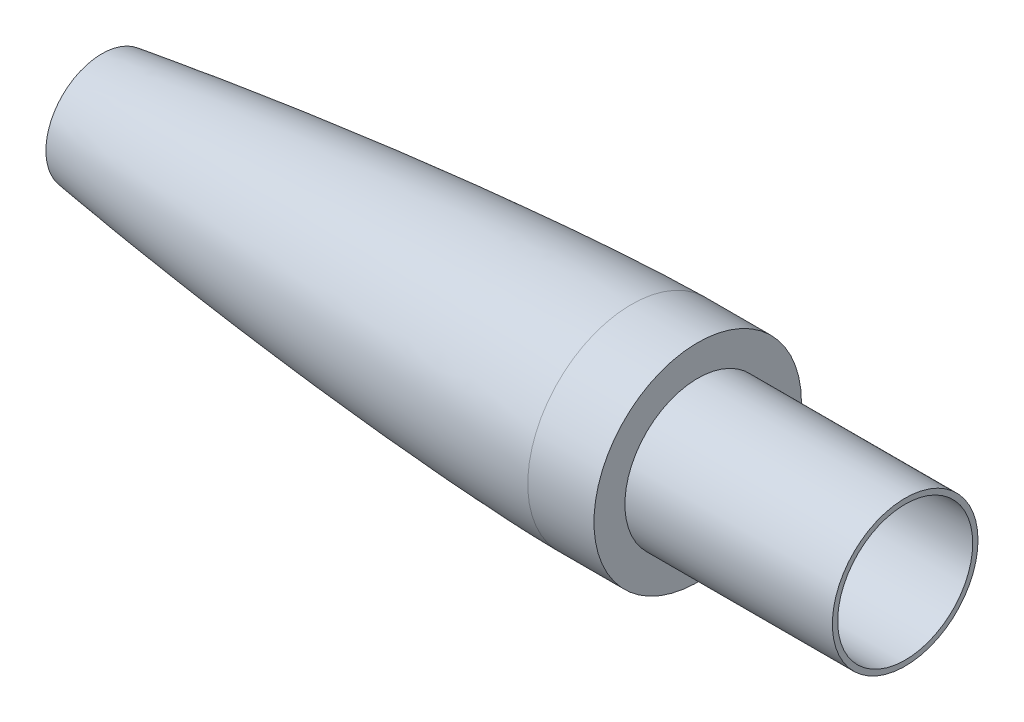
SolidWorks part; units mm, degrees
ref_plane "Front Plane" through (0, 0, 0) normal (0, 0, 1) x (1, 0, 0)
ref_plane "Top Plane" through (0, 0, 0) normal (0, 1, 0) x (1, 0, 0)
ref_plane "Right Plane" through (0, 0, 0) normal (1, 0, 0) x (0, 0, -1)
sketch "Sketch1" plane through (0, 0, 0) normal (0, 0, 1) x (1, 0, 0)
  line L0 (0, 0) -> (600, 0) construction
  line L1 (600, 0) -> (600, 78.36) construction
  line L2 (600, 78.36) -> (650, 78.36)
  line L3 (650, 78.36) -> (650, 55)
  line L4 (650, 55) -> (806.72, 55)
  line L5 (806.72, 55) -> (806.72, 0)
  line L6 (806.72, 0) -> (0, 0)
  line L7 (200, 0) -> (200, 42.3283)
  circle A0 centre (72.0133, 0) radius 20
  spline S0 degree 4 poles (0, 0) (0.0016, 0.0064) (0.0058, 0.0188) (0.0175, 0.0422) (0.0463, 0.0862) (0.0915, 0.1423) (0.1543, 0.2091) (0.2763, 0.3247) (0.4211, 0.4433) (0.5863, 0.5665) (0.8395, 0.741) (1.183, 0.9602) (1.7828, 1.3087) (2.8683, 1.8716) (4.7628, 2.7397) (8.1903, 4.116) (14.423, 6.288) (24.8043, 9.4077) (38.8995, 13.0876) (55.9277, 17.0568) (79.0908, 21.9784) (106.8812, 27.3296) (139.4042, 33.0214) (176.6683, 38.9539) (214.0039, 44.4169) (251.3968, 49.4711) (288.8378, 54.1545) (326.3207, 58.4893) (363.8412, 62.4863) (401.396, 66.1465) (438.983, 69.4606) (476.6007, 72.4071) (509.5423, 74.6287) (537.7965, 76.2335) (560.2923, 77.2755) (575.1954, 77.8326) (587.2142, 78.173) (594.52, 78.3104) (598.1733, 78.3543) (600, 78.36) knots 0 0 0 0 0 0.000043 0.000086 0.000173 0.000345 0.000518 0.00069 0.00128 0.001578 0.001875 0.002717 0.003965 0.006149 0.009932 0.016448 0.028301 0.04964 0.081363 0.112452 0.14354 0.205717 0.267893 0.33007 0.392247 0.454423 0.5166 0.578777 0.640954 0.70313 0.765307 0.827484 0.88966 0.920749 0.951837 0.975919 0.987959 1 1 1 1 1 construction
  spline S1 degree 4 poles (0, 0) (0.0016, 0.0064) (0.0058, 0.0188) (0.0175, 0.0422) (0.0463, 0.0862) (0.0915, 0.1423) (0.1543, 0.2091) (0.2763, 0.3247) (0.4211, 0.4433) (0.5863, 0.5665) (0.8395, 0.741) (1.183, 0.9602) (1.7828, 1.3087) (2.8683, 1.8716) (4.7628, 2.7397) (8.1903, 4.116) (14.423, 6.288) (24.8043, 9.4077) (38.8995, 13.0876) (55.9277, 17.0568) (79.0908, 21.9784) (106.8812, 27.3296) (139.4042, 33.0214) (176.6683, 38.9539) (214.0039, 44.4169) (251.3968, 49.4711) (288.8378, 54.1545) (326.3207, 58.4893) (363.8412, 62.4863) (401.396, 66.1465) (438.983, 69.4606) (476.6007, 72.4071) (509.5423, 74.6287) (537.7965, 76.2335) (560.2923, 77.2755) (575.1954, 77.8326) (587.2142, 78.173) (594.52, 78.3104) (598.1733, 78.3543) (600, 78.36) knots 0 0 0 0 0 0.000043 0.000086 0.000173 0.000345 0.000518 0.00069 0.00128 0.001578 0.001875 0.002717 0.003965 0.006149 0.009932 0.016448 0.028301 0.04964 0.081363 0.112452 0.14354 0.205717 0.267893 0.33007 0.392247 0.454423 0.5166 0.578777 0.640954 0.70313 0.765307 0.827484 0.88966 0.920749 0.951837 0.975919 0.987959 1 1 1 1 1
  dimension "D6" = 40
  dimension "D1" = 78.36
  dimension "D2" = 55
  dimension "D3" = 156.72
  dimension "D4" = 50
  dimension "D5" = 200
revolve "Revolve1" add sketch "Sketch1" angle 360 about L6 region at (509.9374, 32.3829, 0)
sketch "Sketch2" plane through (806.72, 0, 0) normal (1, 0, 0) x (0, 0, -1)
  circle A0 centre (0, 0) radius 51
  circle A1 centre (0, 0) radius 55 construction
  dimension "D1" = 4
extrude "Cut-Extrude1" cut sketch "Sketch2" against normal blind 400 contours A0
sketch "Sketch3" plane through (200, 0, 0) normal (-1, 0, 0) x (0, 0, 1)
  circle A0 centre (0, 20) radius 3.1
  circle A1 centre (0, -20) radius 3.1
  circle A2 centre (0, 0) radius 20 construction
  circle A3 centre (0, 0) radius 33
  dimension "D1" = 6.2
  dimension "D2" = 40
  dimension "D3" = 13
extrude "Cut-Extrude2" cut sketch "Sketch3" against normal blind 40
extrude "Cut-Extrude4" cut sketch "Sketch3<2>" against normal through all contours A0 | A1 region at (200, 20, 0) region at (200, -20, 0)
sketch "Sketch3<2>" plane through (200, 0, 0) normal (-1, 0, 0) x (0, 0, 1) same geometry as "Sketch3"
